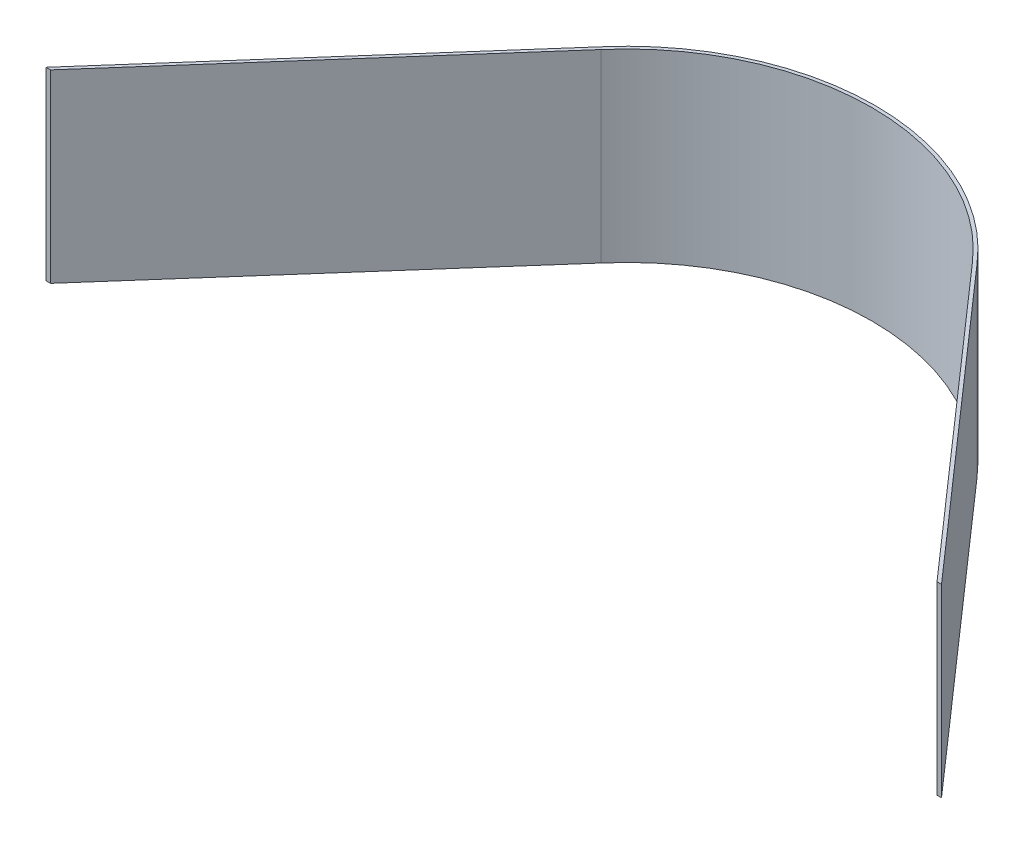
SolidWorks part; units mm, degrees
ref_plane "Front Plane" through (0, 0, 0) normal (0, 0, 1) x (1, 0, 0)
ref_plane "Top Plane" through (0, 0, 0) normal (0, 1, 0) x (1, 0, 0)
ref_plane "Right Plane" through (0, 0, 0) normal (1, 0, 0) x (0, 0, -1)
sketch "Sketch1" plane through (0, 0, 0) normal (0, 1, 0) x (1, 0, 0)
  line L0 (261, 160) -> (110, 331.6587)
  line L1 (110, 331.6587) -> (-110, 331.6587) construction
  line L2 (-110, 331.6587) -> (-261, 160)
  line L3 (261, 160) -> (-261, 160) construction
  line L4 (265.423, 158) -> (111.5092, 332.9711)
  line L5 (-111.5092, 332.9711) -> (-265.423, 158)
  line L7 (-258.7914, 162.5108) -> (-262.7593, 158)
  line L8 (261, 160) -> (262.7592, 158)
  line L9 (-265.423, 158) -> (-262.7593, 158)
  line L10 (262.7592, 158) -> (265.423, 158)
  line L12 (265.423, 158) -> (-265.423, 158) construction
  arc A0 (110, 331.6587) -> (-110, 331.6587) centre (0, 237.0979) ccw
  arc A1 (111.5092, 332.9711) -> (-111.5092, 332.9711) centre (0, 237.0979) ccw
  dimension "D5" = 145.0577
  dimension "D2" = 522
  dimension "D3" = 228.6213
  dimension "D4" = 228.6213
  dimension "D1" = 2
extrude "Boss-Extrude1" add sketch "Sketch1" along normal blind 109.6 contours L4 A1 L5 L9 L7 L2 A0 L0 L8 L10 | L2 A0 L0 L8 L10 L4 A1 L5 L9 L7 region at (185.9332, 0, -246.2105)
equation "\"gap\"= 1mm"
equation "\"casewidth\"= 2mm"
